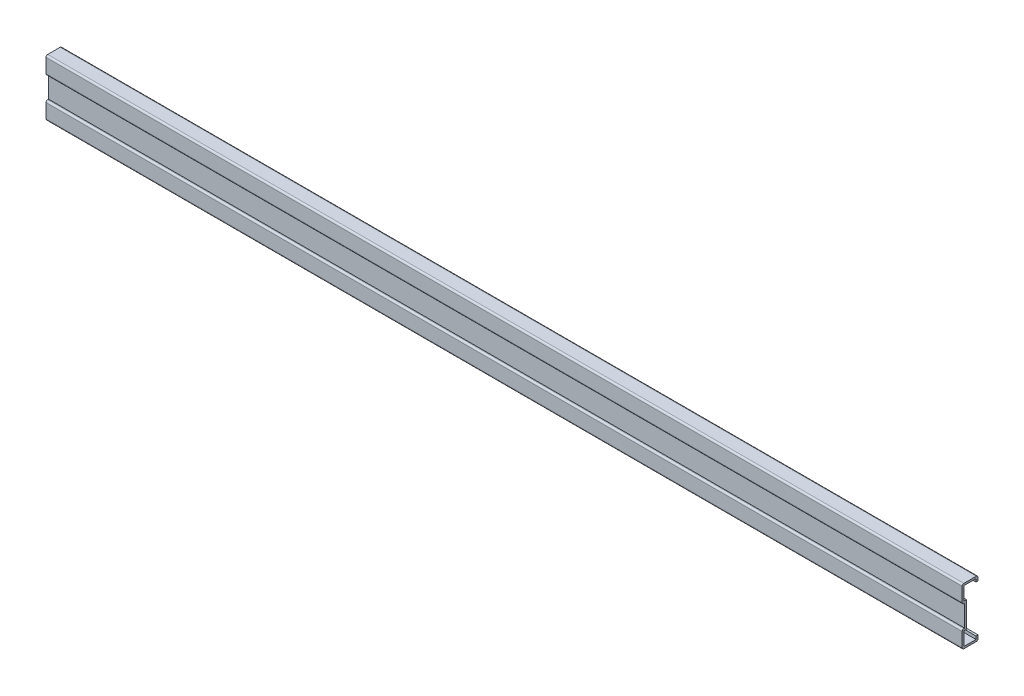
SolidWorks part; units mm, degrees
ref_plane "Спереди" through (0, 0, 0) normal (0, 0, 1) x (1, 0, 0)
ref_plane "Сверху" through (0, 0, 0) normal (0, 1, 0) x (1, 0, 0)
ref_plane "Справа" through (0, 0, 0) normal (1, 0, 0) x (0, 0, -1)
sketch "Эскиз1" plane through (0, 0, 0) normal (1, 0, 0) x (0, 0, -1)
  line L0 (0, 6.5) -> (0, -6.5)
  line L1 (-12.4481, 0) -> (26.4522, 0) construction
  line L2 (0, -6.5) -> (-0.5, -6.5)
  line L3 (-1.5, -7.5) -> (-1.5, -16)
  line L4 (-0.5, -17) -> (7, -17)
  line L5 (8, -16) -> (8, -14)
  line L6 (8, 16) -> (8, 14)
  line L7 (-0.5, 17) -> (7, 17)
  line L8 (-1.5, 7.5) -> (-1.5, 16)
  line L9 (0, 6.5) -> (-0.5, 6.5)
  arc A0 (7, -17) -> (8, -16) centre (7, -16) ccw
  arc A1 (-1.5, -7.5) -> (-0.5, -6.5) centre (-0.5, -7.5) cw
  arc A2 (-1.5, 16) -> (-0.5, 17) centre (-0.5, 16) cw
  arc A3 (-1.5, -16) -> (-0.5, -17) centre (-0.5, -16) ccw
  arc A4 (-1.5, 7.5) -> (-0.5, 6.5) centre (-0.5, 7.5) ccw
  arc A5 (7, 17) -> (8, 16) centre (7, 16) cw
  point P14 (0, 0)
  point P16 (8, -17)
  point P20 (0, 0)
  point P26 (-1.5, -17)
  point P27 (0, 0)
  point P30 (0, 0)
  dimension "D1" = 1
  dimension "D2" = 1
extrude "Вытянуть-Тонкостенный3" add sketch "Эскиз1" along normal blind 550 thin thin type one direction wall 1.2
